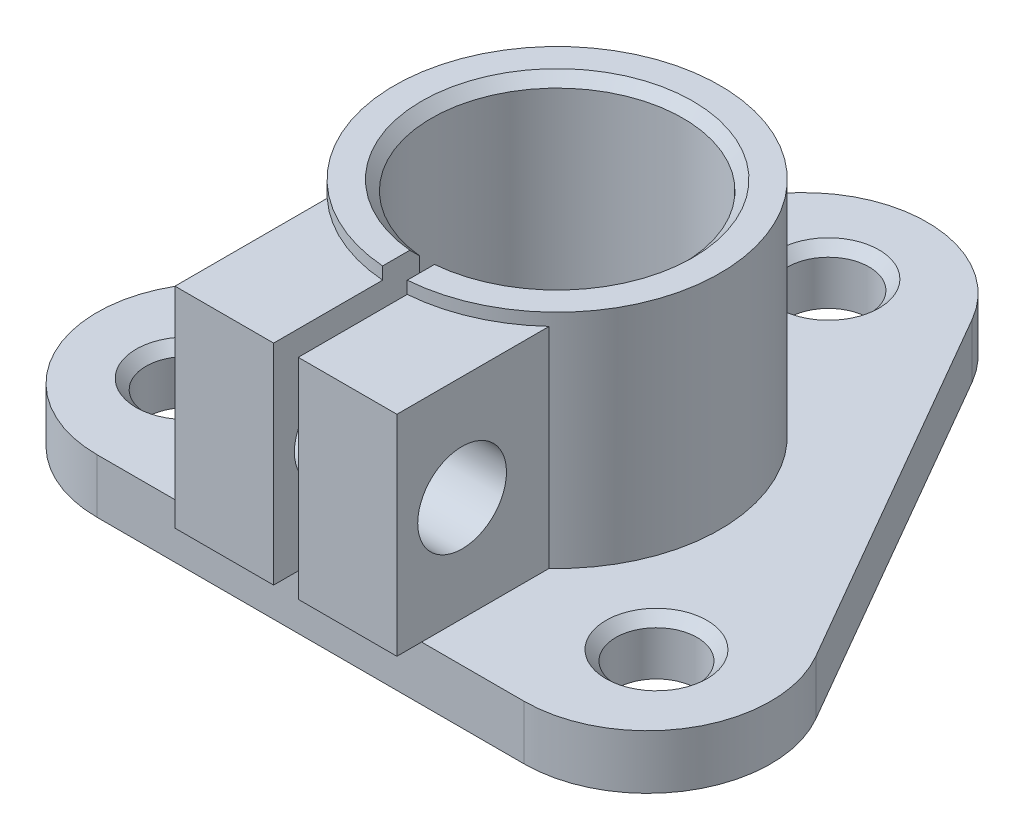
SolidWorks part; units mm, degrees
ref_plane "前视基准面" through (0, 0, 0) normal (0, 0, 1) x (1, 0, 0)
ref_plane "上视基准面" through (0, 0, 0) normal (0, 1, 0) x (1, 0, 0)
ref_plane "右视基准面" through (0, 0, 0) normal (1, 0, 0) x (0, 0, -1)
other "Configuration Table"
sketch "草图1" plane through (0, 0, 0) normal (0, 1, 0) x (1, 0, 0)
  line L1 (17.3205, -10) -> (0, 20)
  line L2 (0, 20) -> (-17.3205, -10)
  line L3 (-17.3205, -10) -> (17.3205, -10)
  circle A1 centre (0, 0) radius 10 construction
  dimension "D1" = 20
extrude "凸台-拉伸1" add sketch "草图1" along normal blind 2.2
sketch "草图2" plane through (0, 2.2, 0) normal (0, 1, 0) x (1, 0, 0)
  circle A0 centre (0, 0) radius 5.1
  dimension "D1" = 10.2
sketch "草图4" plane through (0, 2.2, 0) normal (0, 1, 0) x (1, 0, 0)
  line L0 (0, 0) -> (0, 20) construction
  circle A1 centre (0, 11) radius 1.65
  circle A2 centre (9.5263, -5.5) radius 1.65
  circle A3 centre (-9.5263, -5.5) radius 1.65
  point P17 (0, 0)
  dimension "D1" = 3.3
  dimension "D2" = 11
  dimension "D3" = 3
extrude "切除-拉伸2" cut sketch "草图4" against normal up to next
extrude "切除-拉伸3" cut sketch "草图2" against normal up to next
sketch "草图5" plane through (0, 2.2, 0) normal (0, 1, 0) x (1, 0, 0)
  circle A0 centre (0, 0) radius 5.1 construction
  circle A1 centre (0, 0) radius 5.1
extrude "拉伸-薄壁1" add sketch "草图5" along normal blind 9 thin thin type one direction wall 1.5
fillet "圆角1" radius 5 3 edges at (17.3205, 1.1, 10) (-17.3205, 1.1, 10) (0, 1.1, -20)
sketch "草图6" plane through (0, 11.2, 0) normal (0, 1, 0) x (1, 0, 0)
  line L0 (0, 0) -> (0, -6.6)
  circle A0 centre (0, 0) radius 6.6 construction
  circle A1 centre (0, 0) radius 6.6 construction
extrude "切除-拉伸-薄壁1" cut sketch "草图6" against normal blind 10 thin thin type mid plane wall 1
sketch "草图7" plane through (0, 0, 10) normal (0, 0, 1) x (1, 0, 0)
  line L0 (-0.5, 2.2) -> (-0.5, 11.2) construction
  line L1 (-0.5, 10.7) -> (-4.5, 10.7)
  line L2 (-0.5, 10.7) -> (-0.5, 2.2)
  line L3 (-0.5, 2.2) -> (-4.5, 2.2)
  line L4 (-4.5, 10.7) -> (-4.5, 2.2)
  line L5 (0, -0.1276) -> (0, 11.2) construction
  line L6 (5.1, 11.2) -> (-5.1, 11.2) construction
  line L7 (0.5, 2.2) -> (4.5, 2.2)
  line L8 (4.5, 10.7) -> (4.5, 2.2)
  line L9 (0.5, 10.7) -> (4.5, 10.7)
  line L10 (0.5, 10.7) -> (0.5, 2.2)
  line L12 (-0.5, 2.2) -> (-0.5, 11.2) construction
  line L13 (-0.5, 11.2) -> (-0.5, 1.2) construction
  line L14 (-8.6603, 2.2) -> (8.6603, 2.2) construction
  dimension "D1" = 0.5
  dimension "D2" = 4
extrude "凸台-拉伸2" add sketch "草图7" against normal up to body and the other way blind 1
sketch "草图8" plane through (-4.5, 0, 0) normal (-1, 0, 0) x (0, 0, 1)
  line L0 (4.828, 6.45) -> (11, 6.45) construction
  line L1 (4.828, 10.7) -> (4.828, 2.2) construction
  line L2 (11, 10.7) -> (11, 2.2) construction
  line L3 (8.357, 10.7) -> (8.357, 2.2) construction
  line L7 (11, 10.7) -> (4.828, 10.7) construction
  line L8 (10, 2.2) -> (4.828, 2.2) construction
  circle A0 centre (8.357, 6.45) radius 1.8
  dimension "D1" = 3.6
extrude "切除-拉伸4" cut sketch "草图8" against normal through all
chamfer "倒角1" distance 0.4 angle 45 4 edges at (0, 11.2, -5.1) (0, 2.2, -9.35) (9.5263, 2.2, 7.15) (-9.5263, 2.2, 7.15)
